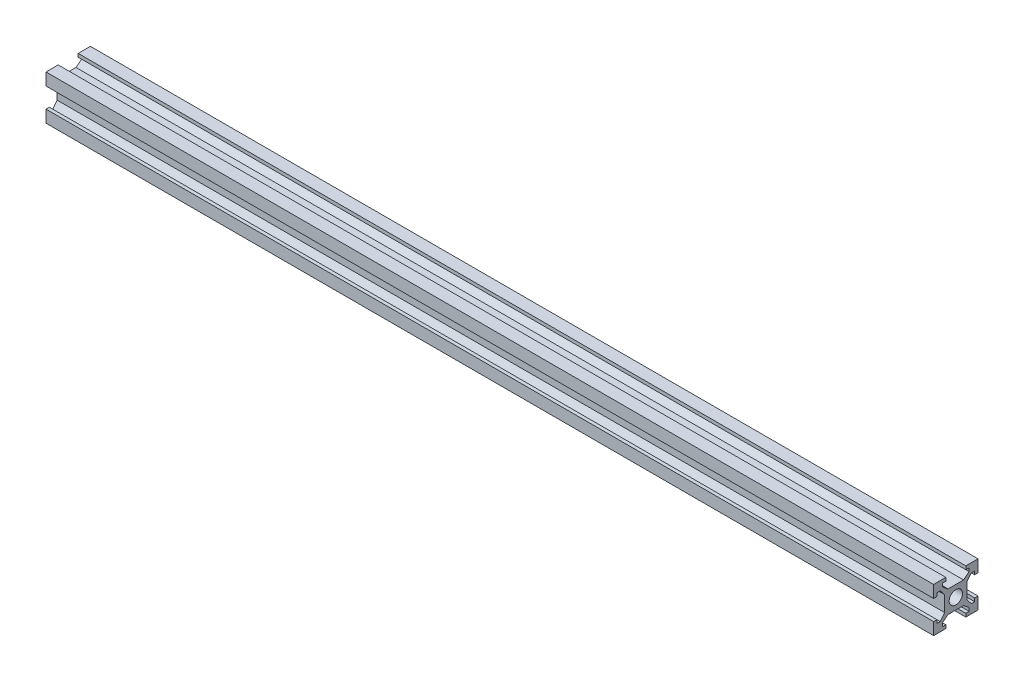
SolidWorks part; units mm, degrees
ref_plane "Front Plane" through (0, 0, 0) normal (0, 0, 1) x (1, 0, 0)
ref_plane "Top Plane" through (0, 0, 0) normal (0, 1, 0) x (1, 0, 0)
ref_plane "Right Plane" through (0, 0, 0) normal (1, 0, 0) x (0, 0, -1)
sketch "Sketch1" plane through (0, 0, 0) normal (1, 0, 0) x (0, 0, -1)
  line L1 (-10, 10) -> (10, 10)
  line L2 (-10, 10) -> (-10, -10)
  line L3 (-10, -10) -> (10, -10)
  line L4 (10, 10) -> (10, -10)
  line L5 (-10, 10) -> (10, -10) construction
  line L6 (-10, -10) -> (10, 10) construction
  point P0 (0, 0)
  dimension "D1" = 20
  dimension "D2" = 20
extrude "Boss-Extrude1" add sketch "Sketch1" along normal blind 400
sketch "Sketch2" plane through (400, 0, 0) normal (1, 0, 0) x (0, 0, -1)
  line L0 (0, 0) -> (0, 10) construction
  line L1 (10, 10) -> (-10, 10) construction
  line L2 (-4.5, 10) -> (-4.5, 8.5)
  line L3 (-4.5, 8.5) -> (-6, 8.5)
  line L4 (-6, 8.5) -> (-6, 7)
  line L5 (-6, 7) -> (-3.5, 5)
  line L6 (-3.5, 5) -> (3.5, 5)
  line L7 (-4.5, 10) -> (4.5, 10)
  line L8 (6, 7) -> (3.5, 5)
  line L9 (6, 8.5) -> (6, 7)
  line L10 (4.5, 8.5) -> (6, 8.5)
  line L11 (4.5, 10) -> (4.5, 8.5)
  circle A0 centre (0, 0) radius 3
  point P14 (0, 5)
  line M2 (10, 10) -> (-10, 10)
  dimension "D1" = 6
  dimension "D2" = 4.5
  dimension "D3" = 3.5
  dimension "D4" = 1.5
  dimension "D5" = 1.5
  dimension "D6" = 2
extrude "Cut-Extrude1" cut sketch "Sketch2" against normal through all contours A0 region at (400, 0, 0)
extrude "Cut-Extrude2" cut sketch "Sketch2<3>" against normal through all contours L0 L6 L8 L9 L10 L11 M2 | L6 L0 L7 L2 L3 L4 L5 region at (400, 7.5256, 2.585) region at (400, 7.5256, -2.585)
sketch "Sketch2<3>" plane through (400, 0, 0) normal (1, 0, 0) x (0, 0, -1) same geometry as "Sketch2"
pattern_circular "CirPattern1" count 4 every 90 about axis through (0, 0, 0) along (1, 0, 0) of "Cut-Extrude2"
